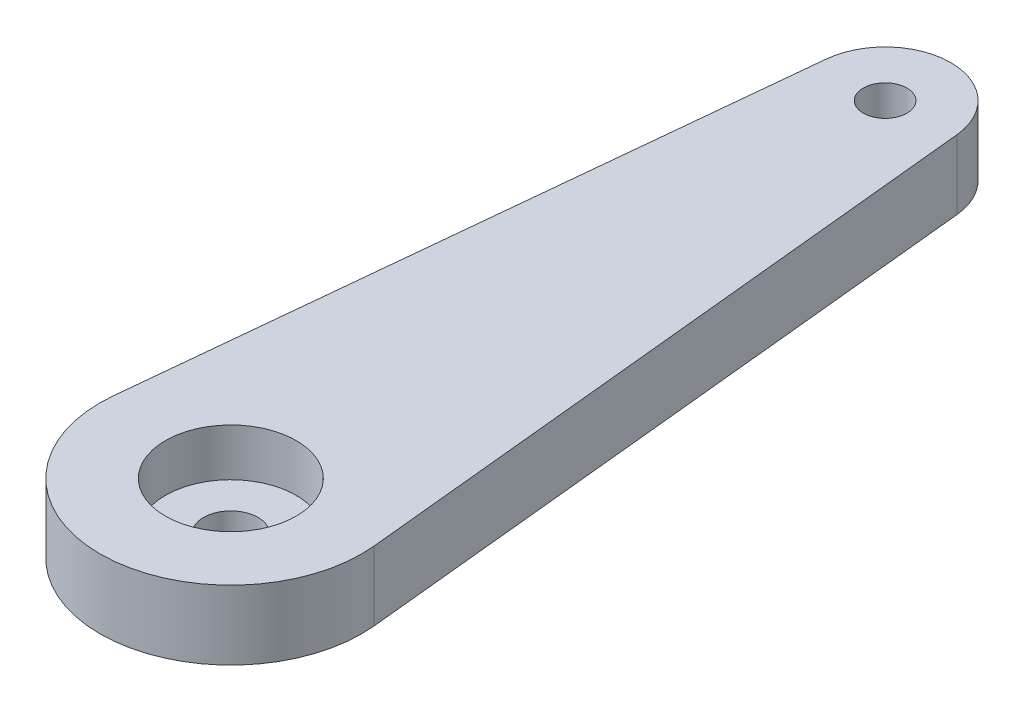
SolidWorks part; units mm, degrees
ref_plane "Front Plane" through (0, 0, 0) normal (0, 0, 1) x (1, 0, 0)
ref_plane "Top Plane" through (0, 0, 0) normal (0, 1, 0) x (1, 0, 0)
ref_plane "Right Plane" through (0, 0, 0) normal (1, 0, 0) x (0, 0, -1)
sketch "Sketch2" plane through (0, 0, 0) normal (0, 1, 0) x (1, 0, 0)
  line L2 (0, 0) -> (0, 30) construction
  line L3 (-3, 30.3) -> (-5.9702, 0.597)
  line L4 (3, 30.3) -> (5.9702, 0.597)
  circle A0 centre (0, 0) radius 1.25
  circle A1 centre (0, 30) radius 1
  arc A2 (-3, 30.3) -> (3, 30.3) centre (0, 30) cw
  arc A3 (-5.9702, 0.597) -> (5.9702, 0.597) centre (0, 0) ccw
  circle A4 centre (0, 0) radius 3
  dimension "D1" = 2.5
  dimension "D2" = 2
  dimension "D6" = 6
  dimension "D5" = 3
  dimension "D3" = 30
  dimension "D4" = 3
extrude "Boss-Extrude1" add sketch "Sketch2" along normal blind 3.175 contours L3 A3 L4 A2 A4 A1 | L3 A3 L4 A2 | A1 | A4 region at (0, 0, -12.3247)
extrude "Boss-Extrude2" add sketch "Sketch2<4>" along normal blind 1 contours A0 A4 region at (-2.9151, 0, 0)
sketch "Sketch2<4>" plane through (0, 0, 0) normal (0, 1, 0) x (1, 0, 0) same geometry as "Sketch2"
